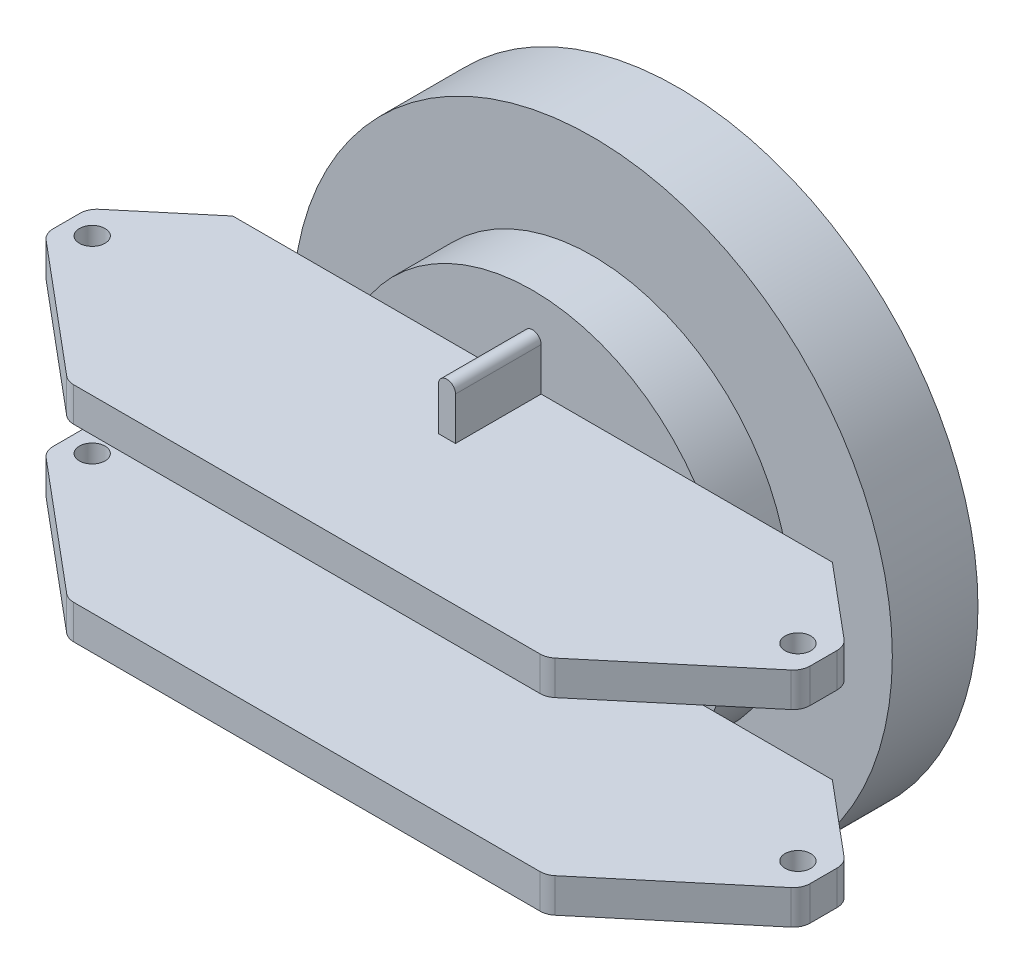
SolidWorks part; units mm, degrees
ref_plane "Front Plane" through (0, 0, 0) normal (0, 0, 1) x (1, 0, 0)
ref_plane "Top Plane" through (0, 0, 0) normal (0, 1, 0) x (1, 0, 0)
ref_plane "Right Plane" through (0, 0, 0) normal (1, 0, 0) x (0, 0, -1)
sketch "Sketch1" plane through (0, 0, 0) normal (0, 0, 1) x (1, 0, 0)
  circle A0 centre (0, 0) radius 35
  dimension "D1" = 70
extrude "Boss-Extrude1" add sketch "Sketch1" along normal blind 10
sketch "Sketch2" plane through (0, 0, 10) normal (0, 0, 1) x (1, 0, 0)
  circle A0 centre (0, 0) radius 23
  dimension "D1" = 46
extrude "Boss-Extrude2" add sketch "Sketch2" along normal blind 7
ref_plane "Plane1" through (0, 13, 0) normal (0, 1, 0) x (1, 0, 0)
sketch "Sketch3" plane through (0, 13, 0) normal (0, 1, 0) x (1, 0, 0)
  line L0 (0, -17) -> (-42.3096, -17) construction
  line L1 (-23, -17) -> (23, -17) construction
  line L2 (0, -17) -> (0, -41.8964) construction
  line L3 (-27.952, -43.3433) -> (27.952, -43.3433)
  line L5 (-35, -17) -> (35, -17)
  line L6 (-44.194, -20.0208) -> (-44.194, -26.3198) construction
  line L7 (-35, -17) -> (-44.194, -24.7147)
  line L8 (-44.194, -24.7147) -> (-44.194, -29.7147)
  line L9 (-44.194, -29.7147) -> (-27.952, -43.3433)
  line L10 (-27.952, -43.3433) -> (-27.952, -17) construction
  line L11 (44.194, -29.7147) -> (27.952, -43.3433)
  line L12 (44.194, -24.7147) -> (44.194, -29.7147)
  line L13 (35, -17) -> (44.194, -24.7147)
  point P12 (0, -43.3433)
  dimension "D1" = 35
  dimension "D2" = 40
  dimension "D3" = 50
  dimension "D4" = 5
  dimension "D5" = 27.952
  dimension "D6" = 44.194
extrude "Boss-Extrude3" add sketch "Sketch3" against normal blind 4
sketch "Sketch4" plane through (0, 13, 0) normal (0, 1, 0) x (1, 0, 0)
  line L0 (0, -17) -> (0, -53.4922) construction
  line L1 (-18.9737, -17) -> (18.9737, -17) construction
  line L2 (-44.194, -27.2147) -> (-41.194, -27.2147) construction
  line L3 (-44.194, -24.7147) -> (-44.194, -29.7147) construction
  line L4 (44.194, -27.2147) -> (41.194, -27.2147) construction
  circle A0 centre (-41.194, -27.2147) radius 1.5
  circle A1 centre (41.194, -27.2147) radius 1.5
  dimension "D1" = 3
  dimension "D2" = 3
extrude "Cut-Extrude1" cut sketch "Sketch4" against normal blind 4
fillet "Fillet1" radius 2 6 edges at (44.194, 11, 24.7147) (44.194, 11, 29.7147) (27.952, 11, 43.3433) (-27.952, 11, 43.3433) (-44.194, 11, 29.7147) (-44.194, 11, 24.7147)
mirror "Mirror1" about plane through (0, 0, 0) normal (0, 1, 0) of "Fillet1", "Cut-Extrude1", "Boss-Extrude3"
sketch "Sketch7" plane through (0, 0, 17) normal (0, 0, 1) x (1, 0, 0)
  line L0 (1, 13) -> (-1, 13)
  line L1 (-27.2241, 13) -> (27.2241, 13) construction
  line L2 (-1, 13) -> (-1, 19)
  line L3 (-1, 19) -> (1, 19)
  line L4 (0, 19) -> (0, 13) construction
  line L5 (1, 13) -> (1, 19)
  dimension "D1" = 6
  dimension "D2" = 1
extrude "Boss-Extrude4" add sketch "Sketch7" along normal blind 10
fillet "Fillet2" 2 edges at (-1, 19, 22) (1, 19, 22) type full round first side face at (-1, 16, 22) second side face at (1, 16, 22) middle face at (0, 19, 22)
mirror "Mirror2" about plane through (0, 0, 0) normal (0, 1, 0) of "Fillet2", "Boss-Extrude4"
sketch "Sketch8" plane through (0, 0, 0) normal (0, 0, -1) x (-1, 0, 0)
  circle A0 centre (0, 0) radius 15
  dimension "D1" = 30
extrude "Cut-Extrude2" cut sketch "Sketch8" against normal blind 10
